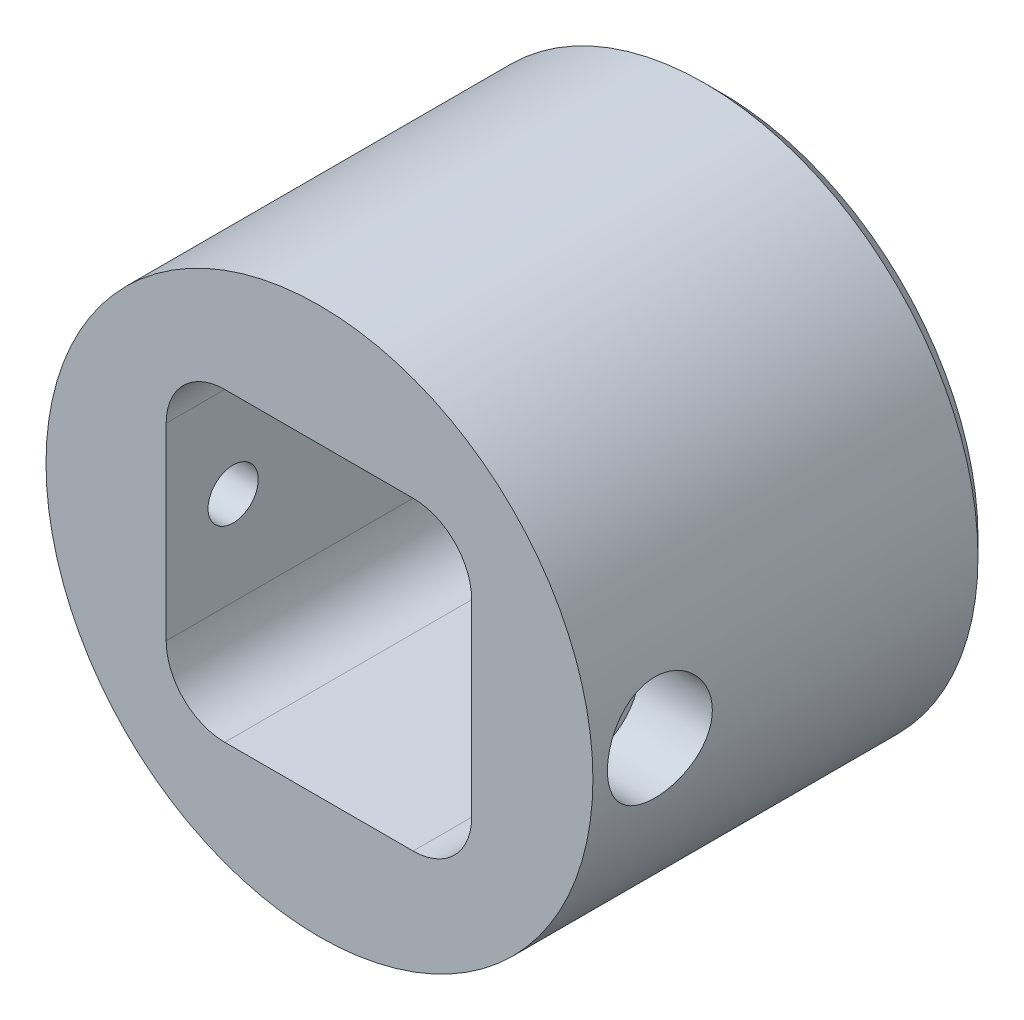
SolidWorks part; units mm, degrees
other "Markup1"
sketch "Sketch5" plane through (11, 11, 18) normal (0, 0.0035, 1) x (1, 0, 0)
material "ABS PC"
ref_plane "Front Plane" through (0, 0, 0) normal (0, 0, 1) x (1, 0, 0)
ref_plane "Top Plane" through (0, 0, 0) normal (0, 1, 0) x (1, 0, 0)
ref_plane "Right Plane" through (0, 0, 0) normal (1, 0, 0) x (0, 0, -1)
sketch "Sketch1" plane through (0, 0, 0) normal (0, 0, 1) x (1, 0, 0)
  circle A1 centre (-4.2426, 4.2426) radius 1.75
  circle A5 centre (0, 0) radius 12.25
  circle A6 centre (4.2426, 4.2426) radius 1.75
  circle A7 centre (4.2426, -4.2426) radius 1.75
  circle A8 centre (-4.2426, -4.2426) radius 1.75
  point P14 (0, 0)
  dimension "D2" = 3.5
  dimension "D3" = 24.5
  dimension "D1" = 4
extrude "Boss-Extrude1" add sketch "Sketch1" along normal blind 18
sketch "Sketch2" plane through (0, 0, 18) normal (0, 0, 1) x (1, 0, 0)
  line L0 (-4.2426, 6.8676) -> (4.1943, 6.8676)
  line L1 (-6.8676, 4.2426) -> (-6.8676, -4.1943)
  line L2 (-4.2426, -6.8193) -> (4.2426, -6.8193)
  line L3 (6.8193, 4.2426) -> (6.8193, -4.2426)
  circle A0 centre (-4.2426, 4.2426) radius 2.625
  circle A4 centre (4.1943, 4.2426) radius 2.625
  circle A5 centre (4.1943, -4.1943) radius 2.625
  circle A6 centre (-4.2426, -4.1943) radius 2.625
  point P15 (-0.0242, 0.0242)
  circle M6 centre (-4.2426, 4.2426) radius 1.75
  circle M14 centre (4.2426, -4.2426) radius 1.75
  circle M15 centre (4.2426, 4.2426) radius 1.75
  circle M16 centre (-4.2426, -4.2426) radius 1.75
  dimension "D1" = 5.25
  dimension "D2" = 4
sketch "Sketch3" plane through (0, 0, 0) normal (1, 0, 0) x (0, 0, -1)
  line L0 (-18, 12.25) -> (-18, -12.25) construction
  circle A0 centre (-15, 0) radius 1.125
  dimension "D1" = 2.25
  dimension "D2" = 3
extrude "Cut-Extrude2" cut sketch "Sketch3" against normal through all both and the other way through all
sketch "Sketch4" plane through (0, 0, 0) normal (1, 0, 0) x (0, 0, -1)
  circle A0 centre (-15, 0) radius 2.35
  dimension "D1" = 4.7
extrude "Cut-Extrude3" cut sketch "Sketch4" against normal blind 5 from offset 9 offset against normal yes
extrude "Cut-Extrude4" cut sketch "Sketch4<2>" along normal blind 5 from offset 9
sketch "Sketch4<2>" plane through (0, 0, 0) normal (1, 0, 0) x (0, 0, -1) same geometry as "Sketch4"
extrude "Cut-Extrude5" cut sketch "Sketch2" against normal blind 16 contours A6 L2 A5 L3 A4 L0 A0 L1 | A4 M15 | A0 M6 | M6 | M16 | A6 M16 | M14 | A5 M14 | M15 region at (-0.0242, 0.0242, 18) region at (-2.439, 6.0463, 18) region at (5.9979, 6.0463, 18) region at (-4.2426, -1.6435, 18) region at (5.9979, -5.9979, 18) region at (-4.2426, 4.2426, 18) region at (4.2426, -4.2426, 18) region at (4.2426, 4.2426, 18) region at (-4.2426, -4.2426, 18)
chamfer "Chamfer1" distance 0.75 angle 45 1 edges at (12.25, 0, 0)
chamfer "Chamfer2" distance 0.5 angle 45 4 edges at (5.9926, -4.2426, 0) (-2.4926, -4.2426, 0) (-2.4926, 4.2426, 0) (5.9926, 4.2426, 0)
